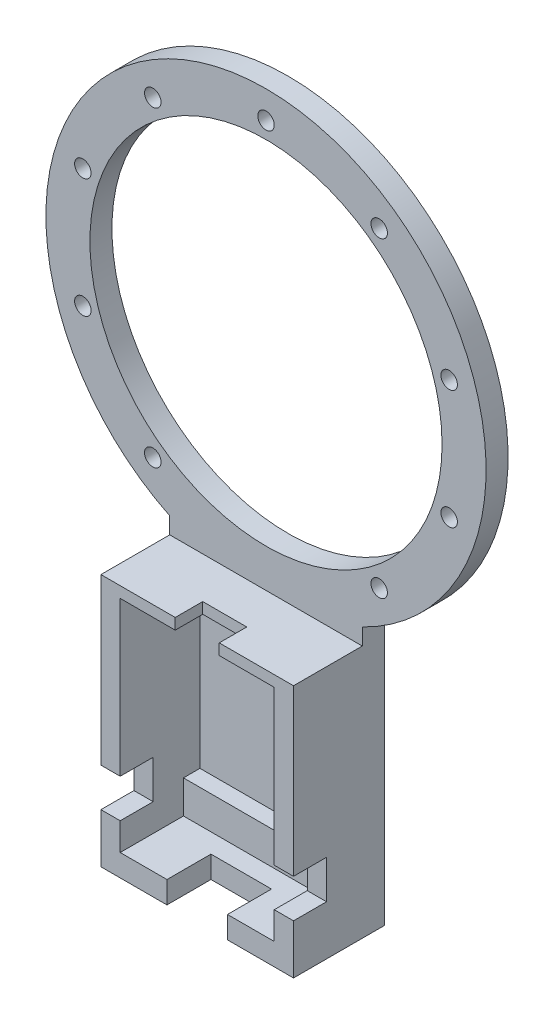
SolidWorks part; units mm, degrees
note: The reader was unsure of these and kept them because the rebuilt part matched: shared geometry of "Sketch1<3>", "Sketch1<11>", "Sketch1<21>".
ref_plane "Front Plane" through (0, 0, 0) normal (0, 0, 1) x (1, 0, 0)
ref_plane "Top Plane" through (0, 0, 0) normal (0, 1, 0) x (1, 0, 0)
ref_plane "Right Plane" through (0, 0, 0) normal (1, 0, 0) x (0, 0, -1)
sketch "Sketch1" plane through (0, 0, 0) normal (0, 0, 1) x (1, 0, 0)
  line L0 (-14, -40.97) -> (14, -40.97)
  line L3 (14, -40.97) -> (14, -80.97)
  line L4 (14, -80.97) -> (-14, -80.97)
  line L5 (-14, -40.97) -> (-14, -80.97)
  line L6 (-14, -80.97) -> (14, -80.97)
  line L7 (-14, -80.97) -> (-14, -74.97)
  line L12 (-14, -74.97) -> (14, -74.97)
  line L13 (14, -80.97) -> (14, -74.97)
  line L14 (14, -40.97) -> (11, -40.97)
  line L15 (14, -40.97) -> (14, -43.97)
  line L16 (14, -43.97) -> (11, -43.97)
  line L17 (11, -40.97) -> (11, -43.97)
  line L18 (-14, -40.97) -> (-11, -40.97)
  line L19 (-14, -40.97) -> (-14, -43.97)
  line L20 (-14, -43.97) -> (-11, -43.97)
  line L21 (-11, -40.97) -> (-11, -43.97)
  line L29 (17.5, -84.97) -> (-17.5, -84.97)
  line L31 (-17.5, -84.97) -> (-17.5, -35.9687)
  line L32 (17.5, -84.97) -> (17.5, -35.9687)
  line L33 (-17.5, -38.97) -> (17.5, -38.97)
  circle A1 centre (0, 0) radius 32
  circle A2 centre (0, -50.97) radius 4
  circle A4 centre (0, 35) radius 1.5
  circle A5 centre (20.5725, 28.3156) radius 1.5
  circle A6 centre (33.287, 10.8156) radius 1.5
  circle A7 centre (33.287, -10.8156) radius 1.5
  circle A8 centre (20.5725, -28.3156) radius 1.5
  circle A10 centre (-20.5725, -28.3156) radius 1.5
  circle A11 centre (-33.287, -10.8156) radius 1.5
  circle A12 centre (-33.287, 10.8156) radius 1.5
  circle A13 centre (-20.5725, 28.3156) radius 1.5
  circle A14 centre (0, -35) radius 1.5 [skipped]
  arc A16 (17.5, -35.9687) -> (-17.5, -35.9687) centre (0, 0) ccw
  point P6 (0, -61.97)
  point P13 (0, 0)
  point P15 (0, -84.97)
  point P34 (0, 0)
  point P49 (0, -82.97)
  point P51 (0, -82.97)
  dimension "D2" = 64
  dimension "D5" = 4
  dimension "D6" = 8
  dimension "D7" = 6
  dimension "D8" = 10
  dimension "D10" = 40.97
  dimension "D9" = 40
  dimension "D3" = 10
  dimension "D4" = 40
  dimension "D11" = 3
  dimension "D12" = 3
  dimension "D13" = 3
  dimension "D14" = 3
  dimension "D15" = 35
  dimension "D16" = 46
extrude "Boss-Extrude1" add sketch "Sketch1" along normal blind 4
extrude "Boss-Extrude2" add sketch "Sketch1<3>" along normal blind 2 separate body contours L0 L21 L20 L5 L12 L3 L16 L17 A2
sketch "Sketch1<3>" plane through (0, 0, 0) normal (0, 0, 1) x (1, 0, 0) same geometry as "Sketch1"
extrude "Boss-Extrude4" add sketch "Sketch1<11>" along normal blind 5 contours L12 L5 L4 L3 | L19 L18 L21 L20 | L15 L14 L17 L16
sketch "Sketch1<11>" plane through (0, 0, 0) normal (0, 0, 1) x (1, 0, 0) same geometry as "Sketch1"
extrude "Boss-Extrude7" add sketch "Sketch1<21>" along normal blind 16.5
sketch "Sketch1<21>" plane through (0, 0, 0) normal (0, 0, 1) x (1, 0, 0) same geometry as "Sketch1"
ref_plane "Plane1" through (17.5, 0, 0) normal (1, 0, 0) x (0, 0, -1)
sketch "Sketch3" plane through (17.5, 0, 0) normal (1, 0, 0) x (0, 0, -1)
  line L0 (-16.5, -84.97) -> (-16.5, -38.97) construction
  line L1 (-16.5, -75.97) -> (-10.5, -75.97)
  line L2 (-16.5, -75.97) -> (-16.5, -68.97)
  line L3 (-16.5, -68.97) -> (-10.5, -68.97)
  line L4 (-10.5, -75.97) -> (-10.5, -68.97)
  line L5 (-16.5, -84.97) -> (0, -84.97) construction
  dimension "D1" = 6
  dimension "D2" = 7
  dimension "D3" = 16
extrude "Cut-Extrude1" cut sketch "Sketch3" against normal blind 35.5
ref_plane "Plane2" through (0, -84.97, 0) normal (0, -1, 0) x (-1, 0, 0)
sketch "Sketch4" plane through (0, -84.97, 0) normal (0, -1, 0) x (-1, 0, 0)
  line L1 (-17.5, -16.5) -> (17.5, -16.5) construction
  line L2 (5.5, -16.5) -> (-5.5, -16.5)
  line L3 (-5.5, -16.5) -> (-5.5, -8.5)
  line L4 (-5.5, -8.5) -> (5.5, -8.5)
  line L5 (5.5, -8.5) -> (5.5, -16.5)
  point P8 (0, -16.5)
  point P9 (0, -16.5)
  dimension "D1" = 11
  dimension "D2" = 8
extrude "Cut-Extrude2" cut sketch "Sketch4" against normal blind 4
sketch "Sketch5" plane through (0, -84.97, 0) normal (0, -1, 0) x (-1, 0, 0)
  line L1 (14, -16.5) -> (-14, -16.5) construction
  line L2 (4, -16.5) -> (-4, -16.5)
  line L3 (-4, -16.5) -> (-4, -11.5)
  line L4 (-4, -11.5) -> (4, -11.5)
  line L5 (4, -11.5) -> (4, -16.5)
  point P8 (0.9385, -16.5)
  point P9 (0, -16.5)
  dimension "D1" = 8
  dimension "D2" = 5
extrude "Cut-Extrude3" cut sketch "Sketch5" against normal blind 52
